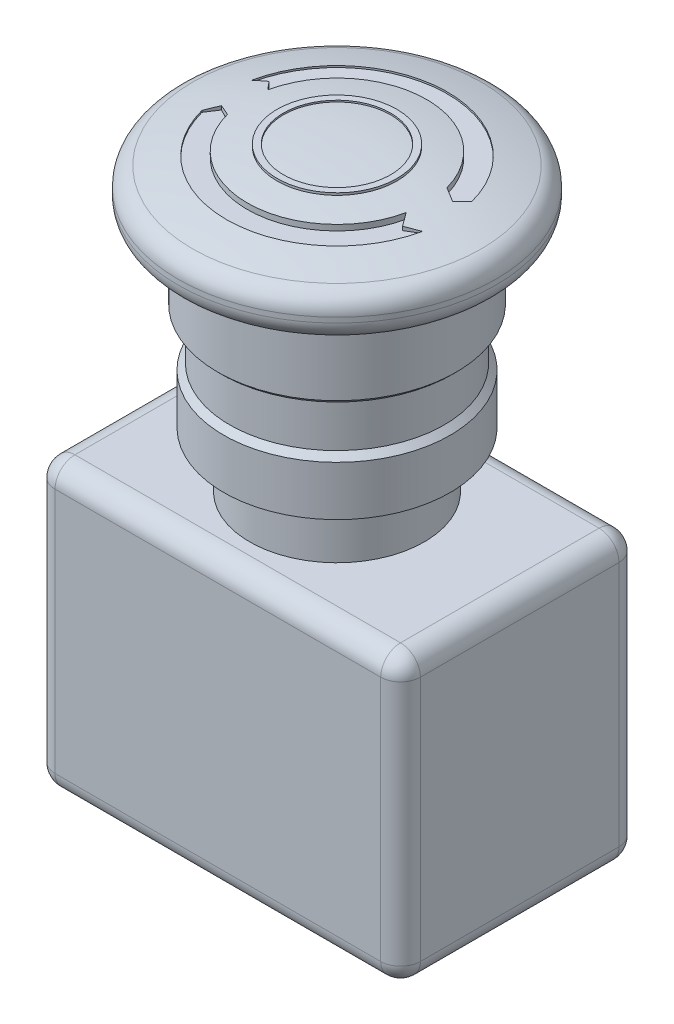
SolidWorks part; units mm, degrees
ref_plane "Спереди" through (0, 0, 0) normal (0, 0, 1) x (1, 0, 0)
ref_plane "Сверху" through (0, 0, 0) normal (0, 1, 0) x (1, 0, 0)
ref_plane "Справа" through (0, 0, 0) normal (1, 0, 0) x (0, 0, -1)
sketch "Эскиз2" plane through (0, 0, 0) normal (0, 0, 1) x (1, 0, 0)
  line L0 (0, 45.754) -> (0, -32.3364) construction
  line L1 (0, 2.9309) -> (20, 2.9309)
  line L2 (20, 2.9309) -> (20, 7.9309)
  line L3 (0, 2.9309) -> (0, 10.9309)
  spline S0 degree 2 poles (20, 7.9309) (10.2367, 11.0049) (0, 10.9309) knots 0 0 0 1 1 1
  dimension "D1" = 20
  dimension "D2" = 8
  dimension "D3" = 5
revolve "Повернуть1" add sketch "Эскиз2" angle 360 about L0
fillet "Скругление2" radius 2.5 2 edges at (0, 2.9309, 20) (0, 7.9309, 20)
ref_plane "Плоскость1" through (0, 13.8129, 0) normal (0, 1, 0) x (1, 0, 0)
sketch "Эскиз5" plane through (0, 13.8129, 0) normal (0, 1, 0) x (1, 0, 0)
  line L0 (-18.1821, 0) -> (21.043, 0) construction
  line L1 (0, 0) -> (-13.6168, 2.8676) construction
  line L2 (0, 0) -> (14.1165, -2.9729) construction
  line L3 (-13.8085, -2.2766) -> (0, 0) construction
  line L4 (0, 0) -> (13.8085, 2.2766) construction
  line L5 (-13.6168, 2.8676) -> (-12.135, 3.59)
  line L6 (-12.135, 3.59) -> (-11.0481, 2.3267)
  line L7 (12.4863, 2.0586) -> (13.4767, 3.4671)
  line L8 (11.0464, -2.3347) -> (12.0666, -3.8135)
  line L9 (12.4863, 2.0586) -> (10.8999, 2.9436)
  line L11 (12.0666, -3.8135) -> (13.6168, -2.8676)
  line L12 (-12.4863, -2.0586) -> (-13.4556, -3.548)
  line L14 (-10.9176, -2.8773) -> (-12.4863, -2.0586)
  arc A0 (-13.4556, -3.548) -> (13.6168, -2.8676) centre (0, 0) ccw
  arc A1 (-10.9176, -2.8773) -> (11.0464, -2.3347) centre (0, 0) ccw
  circle A3 centre (0, 0) radius 12.6549 construction
  arc A4 (10.8999, 2.9436) -> (-11.0481, 2.3267) centre (0, 0) ccw
  arc A5 (13.4767, 3.4671) -> (-13.6168, 2.8676) centre (0, 0) ccw
extrude "Вырез-Вытянуть2" cut sketch "Эскиз5" against normal blind 4.5
sketch "Эскиз6" plane through (0, 2.9309, 0) normal (0, -1, 0) x (1, 0, 0)
  circle A0 centre (0, 0) radius 7.5445
  circle A1 centre (0, 0) radius 6.7426
extrude "Бобышка-Вытянуть2" add sketch "Эскиз6" against normal blind 7.9
sketch "Эскиз7" plane through (0, 2.9309, 0) normal (0, -1, 0) x (1, 0, 0)
  circle A0 centre (0, 0) radius 15
  dimension "D1" = 30
extrude "Бобышка-Вытянуть3" add sketch "Эскиз7" along normal blind 10
chamfer "Фаска1" distance 0.5 angle 45 1 edges at (0, -7.0691, -15)
sketch "Эскиз8" plane through (0, -7.0691, 0) normal (0, -1, 0) x (1, 0, 0)
  circle A0 centre (0, 0) radius 13.5
  dimension "D1" = 27
extrude "Бобышка-Вытянуть4" add sketch "Эскиз8" along normal blind 7
sketch "Эскиз9" plane through (0, -14.0691, 0) normal (0, -1, 0) x (1, 0, 0)
  circle A0 centre (0, 0) radius 14.25
  dimension "D1" = 28.5
extrude "Бобышка-Вытянуть5" add sketch "Эскиз9" along normal blind 6
chamfer "Фаска2" distance 1 angle 45 1 edges at (0, -14.0691, -13.5)
sketch "Эскиз10" plane through (0, -20.0691, 0) normal (0, -1, 0) x (1, 0, 0)
  circle A0 centre (0, 0) radius 11
  dimension "D1" = 22
extrude "Бобышка-Вытянуть6" add sketch "Эскиз10" along normal blind 7
sketch "Эскиз11" plane through (0, -27.0691, 0) normal (0, -1, 0) x (1, 0, 0)
  line L0 (0, 0) -> (0, 15.9373) construction
  line L1 (-23, 15) -> (23, 15)
  line L2 (-23, 15) -> (-23, -15)
  line L3 (-23, -15) -> (23, -15)
  line L4 (23, 15) -> (23, -15)
  line L5 (0, 0) -> (-28.9192, 0) construction
  dimension "D1" = 46
  dimension "D2" = 30
  dimension "D3" = 15
  dimension "D4" = 23
extrude "Бобышка-Вытянуть7" add sketch "Эскиз11" along normal blind 36
fillet "Скругление3" radius 2.5 12 edges at (-23, -63.0691, 0) (-23, -45.0691, -15) (-23, -27.0691, 0) (0, -27.0691, 15) (23, -27.0691, 0) (0, -27.0691, -15) (23, -45.0691, -15) (0, -63.0691, -15) (23, -63.0691, 0) (0, -63.0691, 15) (23, -45.0691, 15) (-23, -45.0691, 15)
